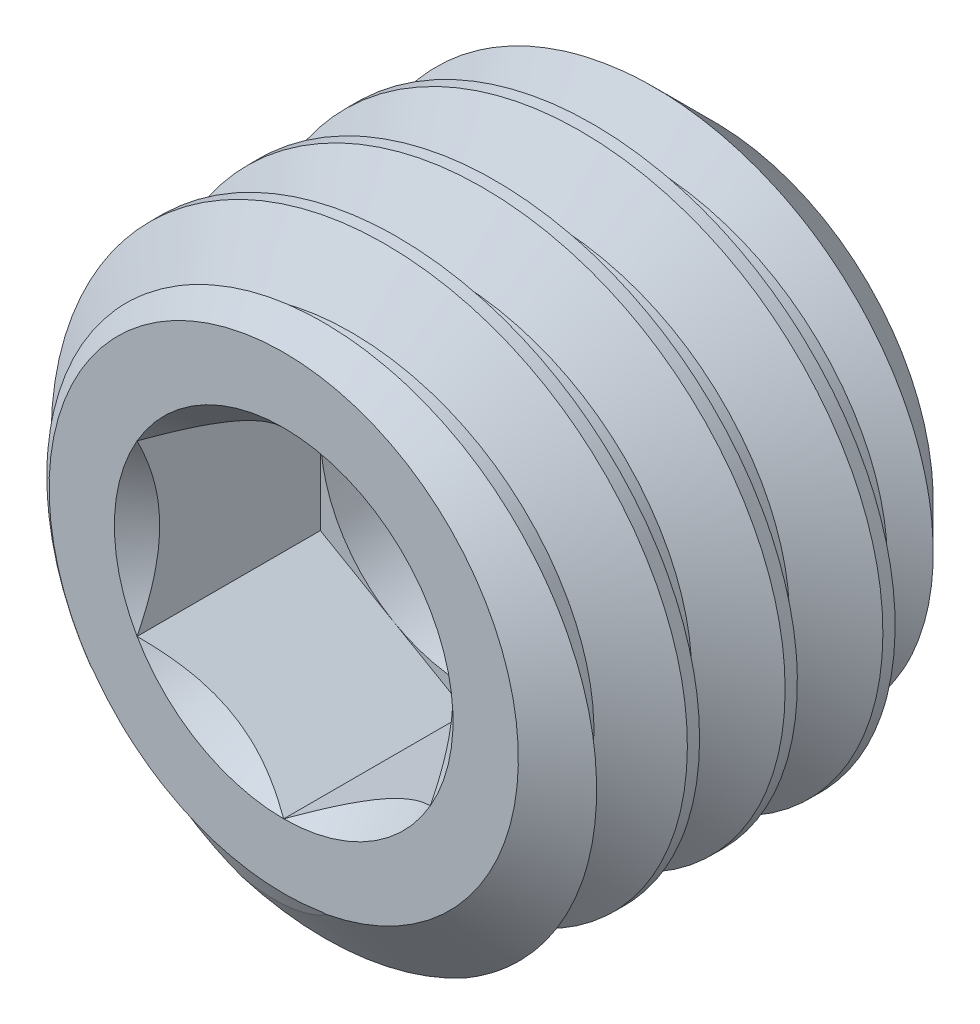
SolidWorks part; units mm, degrees
ref_plane "Front" through (0, 0, 0) normal (0, 0, 1) x (1, 0, 0)
ref_plane "Top" through (0, 0, 0) normal (0, 1, 0) x (1, 0, 0)
ref_plane "Right" through (0, 0, 0) normal (1, 0, 0) x (0, 0, -1)
sketch "Sketch22" plane through (0, 0, 0) normal (1, 0, 0) x (0, 0, -1)
  line L0 (-3.1847, 0) -> (-3.1847, 3.81)
  line L1 (-3.1847, 3.81) -> (-2.5178, 4.7625)
  line L2 (-2.5178, 4.7625) -> (2.6, 4.7625)
  line L3 (2.6, 4.7625) -> (4.7528, 2.6097)
  line L4 (4.7528, 2.6097) -> (3.1847, 0)
  line L5 (3.1847, 0) -> (-3.1847, 0)
  line L6 (3.1847, 0) -> (4.7528, 0) construction
  line L7 (4.7528, 0) -> (4.7528, 2.6097) construction
  line L8 (4.7528, -2.6097) -> (3.1847, 0) construction
  line L9 (-2.5178, -4.7625) -> (2.6, -4.7625) construction
  dimension "Dia" = 9.525
  dimension "Length" = 7.9375
  dimension "D3" = 35
  dimension "D5" = 118
  dimension "D6" = 45
  dimension "D7" = 7.62
revolve "Revolve1" add sketch "Sketch22" angle 360 about L6
ref_plane "Plane1" through (0, 0, -4.7528) normal (0, 0, 1) x (1, 0, 0)
sketch "Sketch27" plane through (0, 0, -4.7528) normal (0, 0, 1) x (1, 0, 0)
  circle A0 centre (0, 0) radius 4.7625 construction
  circle A1 centre (0, 0) radius 4.7625
curve "Helix/Spiral1" pitch 1.5875 height 10.856 radius 4.7625 centre (0, 0, -4.7528) axis (0, 0, 1) start towards (1, 0, 0)
sketch "Sketch28" plane through (0, 0, 0) normal (1, 0, 0) x (0, 0, -1)
  line L0 (4.7528, 4.7625) -> (6.1418, 4.7625)
  line L1 (6.1418, 4.7625) -> (5.5862, 3.8001)
  line L2 (5.5862, 3.8001) -> (5.3084, 3.8001)
  line L3 (5.3084, 3.8001) -> (4.7528, 4.7625)
  line L4 (5.0306, 4.2813) -> (5.864, 4.2813) construction
  line L6 (-2.5178, 4.7625) -> (2.6, 4.7625) construction
  line L7 (4.7528, 5.2388) -> (4.7528, -5.2388) construction
  dimension "D1" = 0.2778
  dimension "D3" = 60
  dimension "D2" = 1.3891
sweep "Cut-Sweep2" cut profiles "Sketch28" path "Helix/Spiral1" align with end faces yes
sketch "Sketch23" plane through (0, 0, 3.1847) normal (0, 0, 1) x (1, 0, 0)
  line L1 (0, 2.7496) -> (-2.3813, 1.3748)
  line L2 (-2.3813, 1.3748) -> (-2.3813, -1.3748)
  line L3 (-2.3813, -1.3748) -> (0, -2.7496)
  line L4 (0, -2.7496) -> (2.3812, -1.3748)
  line L5 (2.3812, -1.3748) -> (2.3812, 1.3748)
  line L6 (2.3812, 1.3748) -> (0, 2.7496)
  circle A0 centre (0, 0) radius 2.3813 construction
  dimension "Hex" = 4.7625
extrude "Cut-Extrude10" cut sketch "Sketch23" against normal blind 2.9766
sketch "Sketch24" plane through (0, 0, 3.1847) normal (0, 0, 1) x (1, 0, 0)
  circle A0 centre (0, 0) radius 2.7496
extrude "Cut-Extrude11" cut sketch "Sketch24" against normal through all draft 45
sketch "Sketch26" plane through (0, 0, 0.2082) normal (0, 0, 1) x (1, 0, 0)
  circle A0 centre (0, 0) radius 2.3813 construction
  circle A1 centre (0, 0) radius 2.3813
extrude "Cut-Extrude12" cut sketch "Sketch26" against normal through all draft 60
sketch "Sketch30" plane through (0, 0, 0) normal (1, 0, 0) x (0, 0, -1)
  line L0 (-2.5178, 4.7625) -> (2.6, 4.7625) construction
  line L1 (-3.1847, 0) -> (-3.1847, 3.81) construction
  line L2 (4.7528, 0) -> (4.7528, 2.6097) construction
  line L3 (-2.5178, -4.7625) -> (2.6, -4.7625) construction
  point P0 (-3.1847, 4.7625)
  point P1 (4.7528, 4.7625)
  point P2 (4.7528, -4.7625)
  point P11 (0.784, -4.7625)
  dimension "D1" = 3.9688
sketch "Sketch31" plane through (0, 0, 0) normal (1, 0, 0) x (0, 0, -1)
  line L2 (3.1847, 0) -> (4.7528, -2.6097)
  line L3 (4.7528, 2.6097) -> (3.1847, 0)
hole_wizard "3/16 (0.1875) Diameter Hole1" positions "3DSketch1" profile "Sketch32" hole size "3/16" standard "ANSI Inch" end condition through all
sketch3d "3DSketch1"
  line L0 (0, 0, 3.1847) -> (0, 0, 2.8163) construction
  point P0 (0, 0, 0)
  point P3 (0, 0, 0)
  point P5 (0, 0, 3.1847)
sketch "Sketch32" plane through (0, 0, 3.1847) normal (1, 0, 0) x (0, -1, 0)
  line L0 (0, 0) -> (0, 7.9375)
  line L1 (0, 7.9375) -> (2.3812, 7.9375)
  line L2 (2.3812, 7.9375) -> (2.3812, 0)
  line L5 (2.3812, 0) -> (0, 0)
  line L11 (0, -6.35) -> (0, 107.95) construction
  dimension "Thru Hole Dia." = 4.7625
  dimension "Thru Hole Depth" = 7.9375
sketch "Sketch33" plane through (0, 0, 0) normal (1, 0, 0) x (0, 0, -1)
  line L0 (0, 0) -> (5.3129, 0) construction
  line L2 (3.81, 0) -> (5.3129, 0)
  line L3 (3.81, 0) -> (3.81, 5.8947)
  line L4 (3.81, 5.8947) -> (5.3129, 5.8947)
  line L5 (5.3129, 0) -> (5.3129, 5.8947)
  dimension "D1" = 3.81
revolve "Cut-Revolve1" cut sketch "Sketch33" angle 360 about L0
equation "\"D7@Sketch22\"=\"Dia@Sketch22\"*.8"
equation "\"D1@Sketch28\" = \"D4@Helix/Spiral1\" * .175"
equation "\"D3@Helix/Spiral1\" = \"Length@Sketch22\" + \"D4@Helix/Spiral1\" + .0524"
equation "\"D1@Sketch30\" = \"D4@Helix/Spiral1\" * 2.5"
equation "\"hex Depth@Cut-Extrude10\" = \"Hex@Sketch23\" * .625"
equation "\"D2@Sketch28\" = \"D4@Helix/Spiral1\" * .875"
